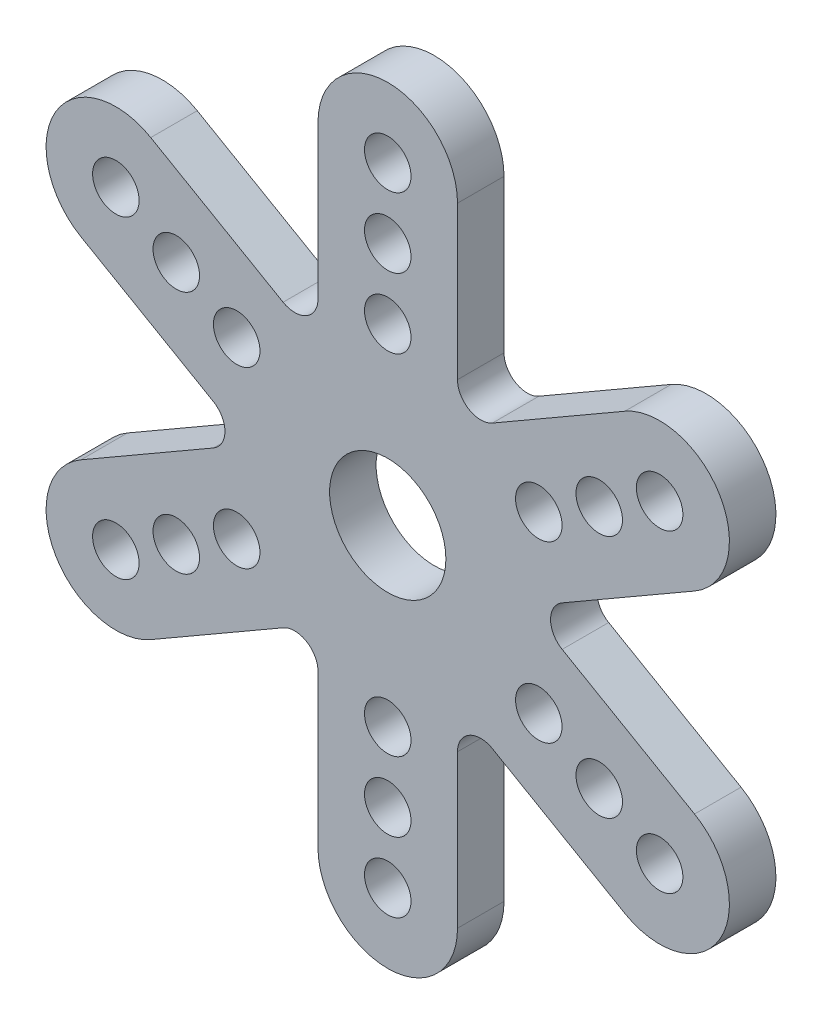
SolidWorks part; units mm, degrees
ref_plane "Front Plane" through (0, 0, 0) normal (0, 0, 1) x (1, 0, 0)
ref_plane "Top Plane" through (0, 0, 0) normal (0, 1, 0) x (1, 0, 0)
ref_plane "Right Plane" through (0, 0, 0) normal (1, 0, 0) x (0, 0, -1)
sketch "Sketch1" plane through (0, 0, 0) normal (0, 0, 1) x (1, 0, 0)
  line L0 (0, 0) -> (0, 15) construction
  line L1 (0, 0) -> (16.5399, 0) construction
  line L2 (0, 7.5) -> (11.544, 7.5) construction
  line L3 (3, 13.5) -> (3, 5.1962)
  line L4 (-3, 13.5) -> (-3, 5.1962)
  line L6 (0, 0) -> (-17.3205, 10) construction
  line L8 (0, 0) -> (-12.1244, 7) construction
  line L9 (0, 0) -> (-17.3205, -10) construction
  line L12 (0, 0) -> (0, -20) construction
  line L13 (0, 0) -> (-12.1244, -7) construction
  line L15 (0, 0) -> (17.3205, -10) construction
  line L17 (0, 0) -> (0, -14) construction
  line L18 (0, 0) -> (17.3205, 10) construction
  line L21 (0, 0) -> (12.1244, -7) construction
  line L24 (0, 0) -> (12.1244, 7) construction
  line L29 (-10.1913, 9.3481) -> (-3, 5.1962)
  line L30 (-13.1913, 4.1519) -> (-6, 0)
  line L31 (-13.1913, -4.1519) -> (-6, 0)
  line L32 (-10.1913, -9.3481) -> (-3, -5.1962)
  line L33 (-3, -13.5) -> (-3, -5.1962)
  line L34 (3, -13.5) -> (3, -5.1962)
  line L35 (10.1913, -9.3481) -> (3, -5.1962)
  line L36 (13.1913, -4.1519) -> (6, 0)
  line L37 (13.1913, 4.1519) -> (6, 0)
  line L38 (10.1913, 9.3481) -> (3, 5.1962)
  circle A1 centre (0, 0) radius 2.5
  circle A29 centre (0, 7.5) radius 1
  arc A30 (3, 13.5) -> (-3, 13.5) centre (0, 13.5) ccw
  circle A31 centre (0, 10.5) radius 1
  circle A32 centre (0, 13.5) radius 1
  circle A33 centre (-6.4952, 3.75) radius 1
  arc A34 (-10.1913, 9.3481) -> (-13.1913, 4.1519) centre (-11.6913, 6.75) ccw
  circle A35 centre (-9.0933, 5.25) radius 1
  circle A36 centre (-11.6913, 6.75) radius 1
  circle A37 centre (-6.4952, -3.75) radius 1
  arc A38 (-13.1913, -4.1519) -> (-10.1913, -9.3481) centre (-11.6913, -6.75) ccw
  circle A39 centre (-9.0933, -5.25) radius 1
  circle A40 centre (-11.6913, -6.75) radius 1
  circle A41 centre (0, -7.5) radius 1
  arc A42 (-3, -13.5) -> (3, -13.5) centre (0, -13.5) ccw
  circle A43 centre (0, -10.5) radius 1
  circle A44 centre (0, -13.5) radius 1
  circle A45 centre (6.4952, -3.75) radius 1
  arc A46 (10.1913, -9.3481) -> (13.1913, -4.1519) centre (11.6913, -6.75) ccw
  circle A47 centre (9.0933, -5.25) radius 1
  circle A48 centre (11.6913, -6.75) radius 1
  circle A49 centre (6.4952, 3.75) radius 1
  arc A50 (13.1913, 4.1519) -> (10.1913, 9.3481) centre (11.6913, 6.75) ccw
  circle A51 centre (9.0933, 5.25) radius 1
  circle A52 centre (11.6913, 6.75) radius 1
  dimension "D1" = 7.5
  dimension "D3" = 3
  dimension "D2" = 3
extrude "Extrude1" add sketch "Sketch1" along normal blind 2
ref_axis "Axis1" through (0, 0, 2) along (0, 0, -1)
fillet "Fillet1" radius 1 6 edges at (3, 5.1962, 1) (6, 0, 1) (3, -5.1962, 1) (-3, -5.1962, 1) (-6, 0, 1) (-3, 5.1962, 1)
